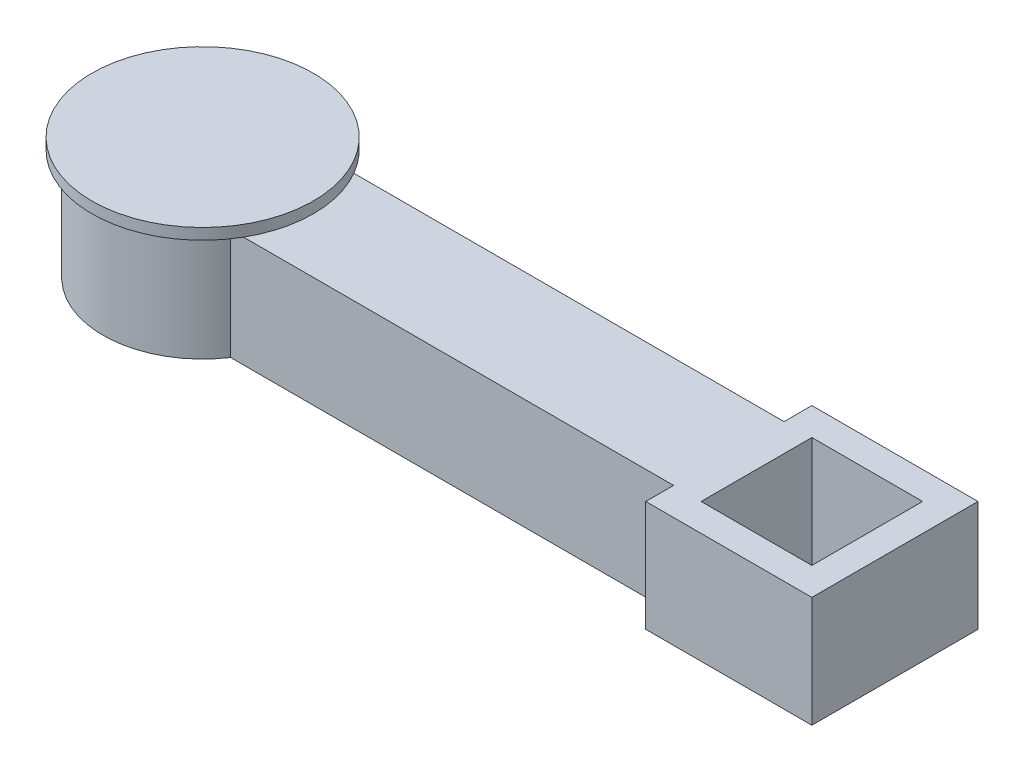
SolidWorks part; units mm, degrees
ref_plane "Front Plane" through (0, 0, 0) normal (0, 0, 1) x (1, 0, 0)
ref_plane "Top Plane" through (0, 0, 0) normal (0, 1, 0) x (1, 0, 0)
ref_plane "Right Plane" through (0, 0, 0) normal (1, 0, 0) x (0, 0, -1)
sketch "Sketch1" plane through (0, 0, 0) normal (0, 1, 0) x (1, 0, 0)
  line L0 (163.1456, 275.7418) -> (163.1456, 275.9924)
  line L1 (163.1456, 175.9924) -> (563.1456, 175.9924)
  line L2 (163.1456, 175.9924) -> (163.1456, 176.2431)
  line L3 (163.1456, 275.9924) -> (563.1456, 275.9924)
  line L4 (563.1456, 175.9924) -> (563.1456, 176.2431)
  line L5 (563.1456, 275.7418) -> (563.1456, 275.9924)
  line L8 (163.1456, 275.9924) -> (563.1456, 275.9924)
  line L9 (163.1456, 275.9924) -> (163.1456, 275.7418)
  line L10 (163.1456, 176.2431) -> (563.1456, 176.2431)
  line L11 (563.1456, 275.9924) -> (563.1456, 176.2431)
  line L12 (563.1456, 301.1178) -> (713.1456, 301.1178)
  line L13 (563.1456, 301.1178) -> (563.1456, 151.1178)
  line L14 (563.1456, 151.1178) -> (713.1456, 151.1178)
  line L15 (713.1456, 301.1178) -> (713.1456, 151.1178)
  arc A0 (163.1456, 275.7418) -> (163.1456, 176.2431) centre (88.1456, 225.9924) ccw
  point P13 (713.1456, 226.1178)
  point P14 (563.1456, 226.1178)
  dimension "D3" = 180
  dimension "D6" = 150
  dimension "D1" = 400
  dimension "D2" = 100
  dimension "D4" = 50
  dimension "D5" = 75
  dimension "D7" = 150
extrude "Boss-Extrude1" add sketch "Sketch1" along normal blind 100 contours L0 A0 L10 L11 L5 L3 | L13 L12 L15 L14 region at (257.4243, 0, -226.0702)
sketch "Sketch5" plane through (0, 100, 0) normal (0, 1, 0) x (1, 0, 0)
  circle A0 centre (88.1456, 225.9924) radius 70
  dimension "D1" = 140
extrude "Cut-Extrude2" cut sketch "Sketch5" against normal blind 100
sketch "Sketch6" plane through (0, 100, 0) normal (0, 1, 0) x (1, 0, 0)
  circle A0 centre (88.1456, 225.9924) radius 100
  dimension "D1" = 200
extrude "Boss-Extrude4" add sketch "Sketch6" along normal blind 10
sketch "Sketch7" plane through (0, 100, 0) normal (0, 1, 0) x (1, 0, 0)
  line L0 (563.1456, 301.1178) -> (713.1456, 301.1178) construction
  line L1 (588.1456, 176.1178) -> (688.1456, 176.1178)
  line L2 (588.1456, 176.1178) -> (588.1456, 276.1178)
  line L3 (588.1456, 276.1178) -> (688.1456, 276.1178)
  line L4 (688.1456, 176.1178) -> (688.1456, 276.1178)
  line L5 (713.1456, 301.1178) -> (713.1456, 151.1178) construction
  point P6 (638.1456, 301.1178)
  point P7 (638.1456, 276.1178)
  point P10 (713.1456, 226.1178)
  point P11 (688.1456, 226.1178)
  dimension "D1" = 100
  dimension "D2" = 100
extrude "Cut-Extrude3" cut sketch "Sketch7" against normal blind 100
